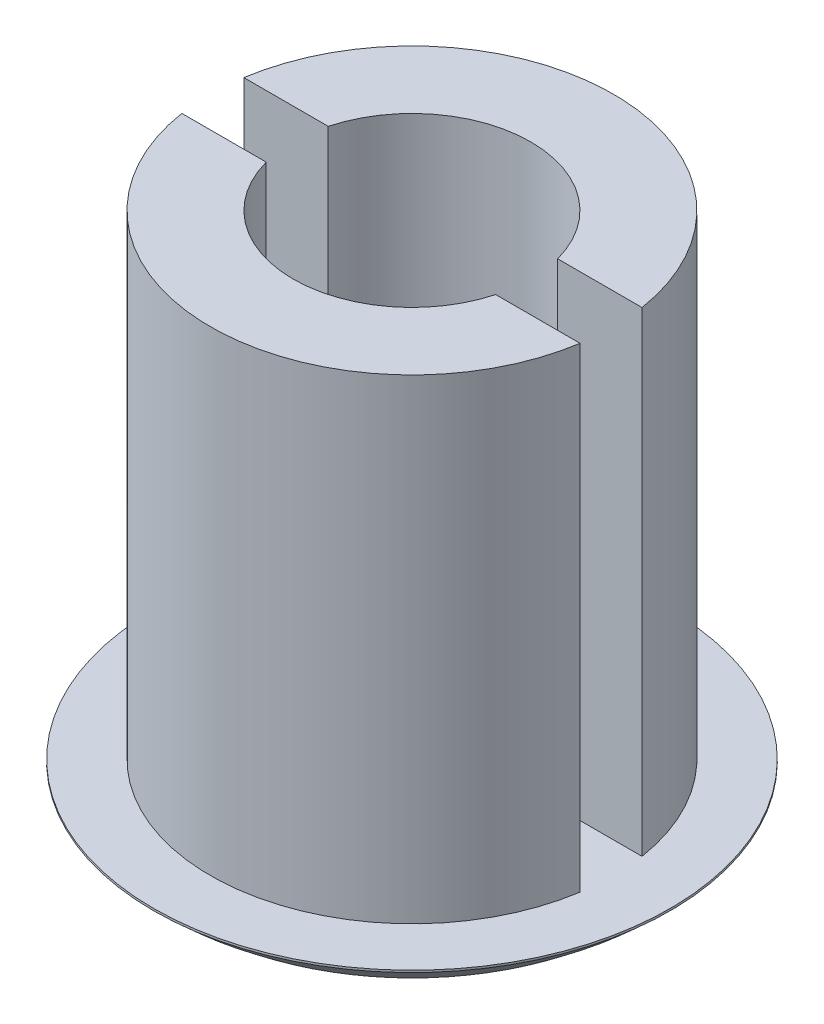
SolidWorks part; units mm, degrees
ref_plane "Front Plane" through (0, 0, 0) normal (0, 0, 1) x (1, 0, 0)
ref_plane "Top Plane" through (0, 0, 0) normal (0, 1, 0) x (1, 0, 0)
ref_plane "Right Plane" through (0, 0, 0) normal (1, 0, 0) x (0, 0, -1)
sketch "Sketch1" plane through (0, 0, 0) normal (0, 1, 0) x (1, 0, 0)
  circle A0 centre (0, 0) radius 12.5
  dimension "D1" = 25
extrude "Boss-Extrude1" add sketch "Sketch1" along normal blind 0.1
dome "Dome1" faces to dome 1 distance 5 reverse direction no elliptical dome no face at (0, 0, 12.5) parameters "D1"=5
sketch "Sketch2" plane through (0, 0.1, 0) normal (0, 1, 0) x (1, 0, 0)
  circle A0 centre (0, 0) radius 9.75
  dimension "D1" = 19.5
extrude "Boss-Extrude2" add sketch "Sketch2" along normal blind 23
shell "Shell3" thickness 4 removed face at (0, 23.1, 9.75)
sketch "Sketch3" plane through (0, 23.1, 0) normal (0, 1, 0) x (1, 0, 0)
  line L1 (-10.6401, 1.5) -> (11.7545, 1.5)
  line L2 (-10.6401, 1.5) -> (-10.6401, -1.5)
  line L3 (-10.6401, -1.5) -> (11.7545, -1.5)
  line L4 (11.7545, 1.5) -> (11.7545, -1.5)
  dimension "D1" = 1.5
  dimension "D2" = 1.5
  dimension "D3" = 22.3946
extrude "Cut-Extrude1" cut sketch "Sketch3" against normal up to surface (23 mm away) up to face at (0, 0.1, 9.75)
